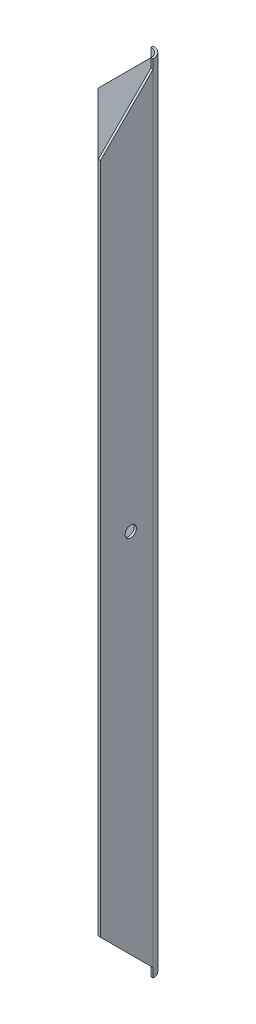
SolidWorks part; units mm, degrees
ref_plane "Front" through (0, 0, 0) normal (0, 0, 1) x (1, 0, 0)
ref_plane "Top" through (0, 0, 0) normal (0, 1, 0) x (1, 0, 0)
ref_plane "Right" through (0, 0, 0) normal (1, 0, 0) x (0, 0, -1)
sketch "Sketch1" plane through (0, 0, 0) normal (1, 0, 0) x (0, 0, -1)
  line L0 (0, -300) -> (0, 300)
  line L1 (0, 0) -> (55, 0) construction
  line L2 (55, 355) -> (55, -355)
  line L3 (55, 355) -> (0, 300)
  line L4 (0, -300) -> (55, -355)
  line L6 (55, 355) -> (57, 355)
  line L7 (55, 355) -> (55, -355)
  line L8 (55, -355) -> (57, -355)
  line L9 (57, 355) -> (57, -355)
  point P4 (0, 0)
  point P9 (55, 0)
  dimension "D1" = 710
  dimension "D2" = 55
  dimension "D3" = 45
  dimension "D4" = 2
extrude "Boss-Extrude1" add sketch "Sketch1" along normal blind 2 contours L0 L1 L2 L3 | L1 L0 L4 L7 | L9 L6 L2 L7 L8 region at (0, -164.1349, -28.2697) region at (0, 164.1349, -28.2697) region at (0, 0, -56)
sketch "Sketch2" plane through (0, 0, -57) normal (0, 0, -1) x (-1, 0, 0)
  line L0 (0, 0) -> (55, 0) construction
  line L1 (55, 300) -> (55, -300)
  line L2 (55, 300) -> (0, 355)
  line L3 (55, -300) -> (0, -355)
  line L4 (0, -355) -> (0, 355)
  point P6 (55, 0)
  dimension "D1" = 55
  dimension "D2" = 45
extrude "Boss-Extrude3" add sketch "Sketch2" against normal blind 2
ref_plane "Plane1" through (0, 0, 0) normal (0, -1, 0) x (-1, 0, 0)
sketch "Sketch3" plane through (0, 0, 0) normal (0, -1, 0) x (-1, 0, 0)
  line L0 (8, 57) -> (-2, 57)
  line L1 (0, 57) -> (55, 57) construction
  line L2 (-2, 0) -> (-2, 55) construction
  line L3 (-2, 57) -> (-2, 47)
  arc A0 (8, 57) -> (-2, 47) centre (8, 47) ccw
  dimension "D1" = 10
extrude "Cut-Extrude2" cut sketch "Sketch3" against normal up to next and the other way up to next
sketch "Sketch6" plane through (0, 0, 0) normal (0, -1, 0) x (-1, 0, 0)
  line L0 (8, 57) -> (55, 57) construction
  line L1 (-2, 0) -> (-2, 47) construction
  line L2 (8, 55) -> (8, 57)
  line L3 (0, 47) -> (-2, 47)
  arc A0 (8, 57) -> (-2, 47) centre (8, 47) ccw
  arc A1 (8, 55) -> (0, 47) centre (8, 47) ccw
  dimension "D1" = 20
  dimension "D2" = 16
extrude "Boss-Extrude5" add sketch "Sketch6" along normal blind 355 and the other way blind 355 contours A0 L3 A1 L2
sketch "Sketch7" plane through (0, 0, -57) normal (0, 0, -1) x (-1, 0, 0)
  line L0 (-36.6737, 0) -> (36.6737, 0) construction
  line L1 (8, -347) -> (8, 347) construction
  circle A0 centre (28, 0) radius 5
  dimension "D2" = 10
  dimension "D1" = 20
extrude "Cut-Extrude3" cut sketch "Sketch7" against normal blind 355
sketch "Sketch8" plane through (2, 0, 0) normal (1, 0, 0) x (0, 0, -1)
  line L0 (-36.6737, 0) -> (36.6737, 0) construction
  line L1 (47, -347) -> (47, 347) construction
  circle A0 centre (27, 0) radius 5
  dimension "D1" = 10
  dimension "D2" = 20
extrude "Cut-Extrude4" cut sketch "Sketch8" against normal blind 355
